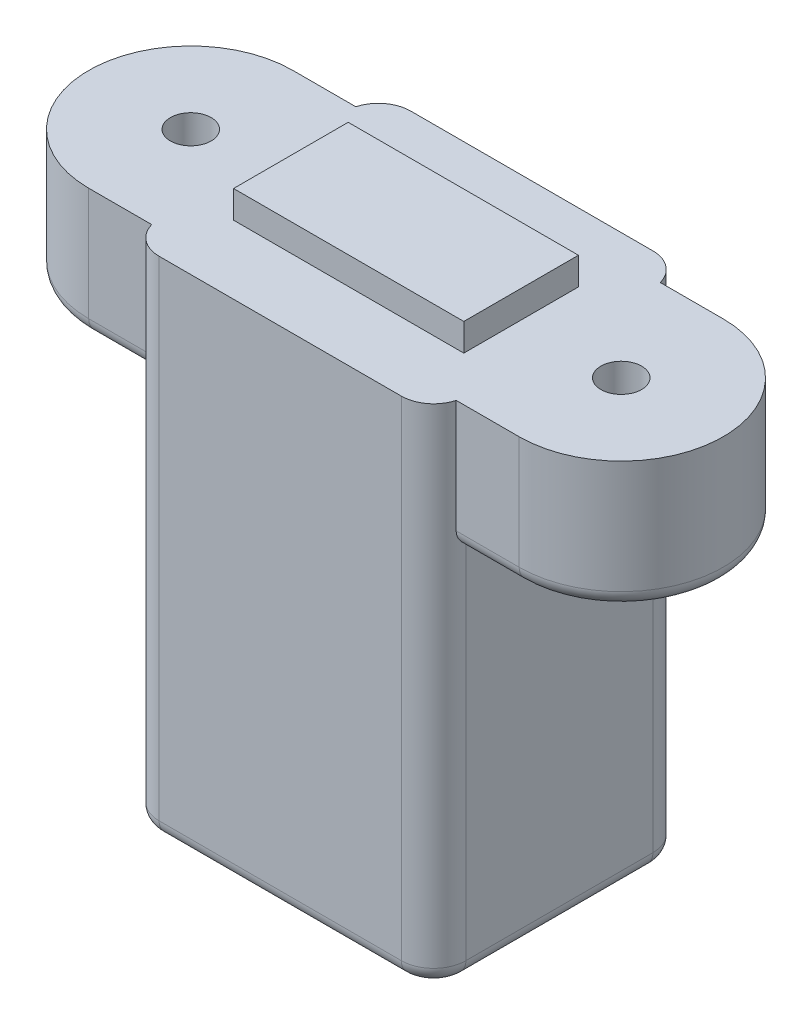
SolidWorks part; units mm, degrees
ref_plane "Front" through (0, 0, 0) normal (0, 0, 1) x (1, 0, 0)
ref_plane "Top" through (0, 0, 0) normal (0, 1, 0) x (1, 0, 0)
ref_plane "Right" through (0, 0, 0) normal (1, 0, 0) x (0, 0, -1)
sketch "Sketch1" plane through (0, 0, 0) normal (0, 1, 0) x (1, 0, 0)
  line L1 (8.4645, -4.0132) -> (-8.4646, -4.0132)
  line L3 (8.4645, 4.0132) -> (-8.4646, 4.0132)
  line L5 (8.4645, -4.0132) -> (-8.4646, 4.0132) construction
  line L6 (8.4645, 4.0132) -> (-8.4646, -4.0132) construction
  arc A0 (-8.4646, 4.0132) -> (-8.4646, -4.0132) centre (-8.4646, 0) ccw
  arc A1 (8.4645, 4.0132) -> (8.4645, -4.0132) centre (8.4645, 0) cw
  point P0 (0, 0)
  point P2 (-12.4778, 0)
  point P7 (0, 0)
  point P10 (12.4777, 0)
  point P11 (0, 0)
  point P12 (0, 0)
  point P13 (0, 0)
  point P14 (-8.255, 4.0132)
  point P15 (0, 0)
  point P16 (0, 0)
  dimension "D3" = 24.9555
  dimension "D1" = 8.0264
extrude "Boss-Extrude1" add sketch "Sketch1" along normal blind 5.08 contours L3 A0 L1 A1
ref_axis "Axis1" through (-8.4646, 5.08, 0) along (0, -1, 0)
ref_axis "Axis2" through (8.4645, 5.08, 0) along (0, -1, 0)
hole_wizard "M2x0.4 Tapped Hole1" positions "Sketch6" profile "Sketch7" tap size "M2x0.4" standard "ANSI Metric" end condition through all
sketch "Sketch6" plane through (0, 5.08, 0) normal (0, 1, 0) x (1, 0, 0)
  point P0 (-8.4646, 0)
  point P2 (8.4645, 0)
sketch "Sketch7" plane through (-8.4646, 5.08, 0) normal (1, 0, 0) x (0, 0, 1)
  line L0 (0, 0) -> (0, 5.08)
  line L1 (0, 5.08) -> (0.8, 5.08)
  line L2 (0.8, 5.08) -> (0.8, 0)
  line L5 (0.8, 0) -> (0, 0)
  line L11 (0, -6.35) -> (0, 107.95) construction
  dimension "Thru Tap Drill Dia." = 1.6
  dimension "Thru Tap Drill Depth" = 5.08
cosmetic thread "Hole Thread1" parameters "D2"=2
cosmetic thread "Hole Thread2" parameters "D2"=2
sketch "Sketch8" plane through (0, 5.08, 0) normal (0, 1, 0) x (1, 0, 0)
  line L1 (6.0325, -4.9466) -> (-6.0325, -4.9466)
  line L2 (6.0325, -4.9466) -> (6.0325, 4.9467)
  line L3 (6.0325, 4.9467) -> (-6.0325, 4.9466)
  line L4 (-6.0325, -4.9466) -> (-6.0325, 4.9466)
  line L5 (6.0325, -4.9466) -> (-6.0325, 4.9466) construction
  line L6 (6.0325, 4.9467) -> (-6.0325, -4.9466) construction
  point P0 (0, 0)
  dimension "D1" = 12.065
  dimension "D2" = 9.8933
extrude "Boss-Extrude2" add sketch "Sketch8" against normal blind 19.8628
fillet "Fillet1" radius 1.27 4 edges at (-6.0325, -4.8514, 4.9466) (6.0325, -4.8514, 4.9466) (-6.0325, -4.8514, -4.9466) (6.0325, -4.8514, -4.9467)
fillet "Fillet2" radius 0.635 6 edges at (-7.2258, 0, 4.0132) (-12.4778, 0, 0) (-7.2258, 0, -4.0132) (7.2258, 0, -4.0132) (7.2258, 0, 4.0132) (12.4777, 0, 0)
fillet "Fillet3" radius 0.635 8 edges at (5.6605, -14.7828, 4.5747) (6.0325, -14.7828, 0) (5.6605, -14.7828, -4.5747) (0, -14.7828, -4.9467) (-5.6605, -14.7828, -4.5747) (-6.0325, -14.7828, 0) (-5.6605, -14.7828, 4.5747) (0, -14.7828, 4.9466)
sketch "Sketch9" plane through (0, 5.08, 0) normal (0, 1, 0) x (1, 0, 0)
  line L0 (4.7625, 4.9467) -> (-4.7625, 4.9466) construction
  line L1 (-4.5276, -2.2543) -> (4.5275, -2.2543)
  line L2 (-4.5276, -2.2543) -> (-4.5276, 2.2542)
  line L3 (-4.5276, 2.2542) -> (4.5275, 2.2542)
  line L4 (4.5275, -2.2543) -> (4.5275, 2.2542)
  line L5 (-4.5276, -2.2543) -> (4.5275, 2.2542) construction
  line L6 (-4.5276, 2.2542) -> (4.5275, -2.2543) construction
  arc A0 (-8.4646, 4.0132) -> (-8.4646, -4.0132) centre (-8.4646, 0) ccw construction
  point P0 (0, 0)
  point P7 (0, 4.9467)
  point P11 (-12.4778, 0)
  dimension "D1" = 9.0551
  dimension "D2" = 4.5085
extrude "Boss-Extrude3" add sketch "Sketch9" along normal blind 1.0795
ref_plane "Plane1" through (-4.7625, 5.08, -4.9466) normal (-1, 0, 0) x (0, 0, 1)
